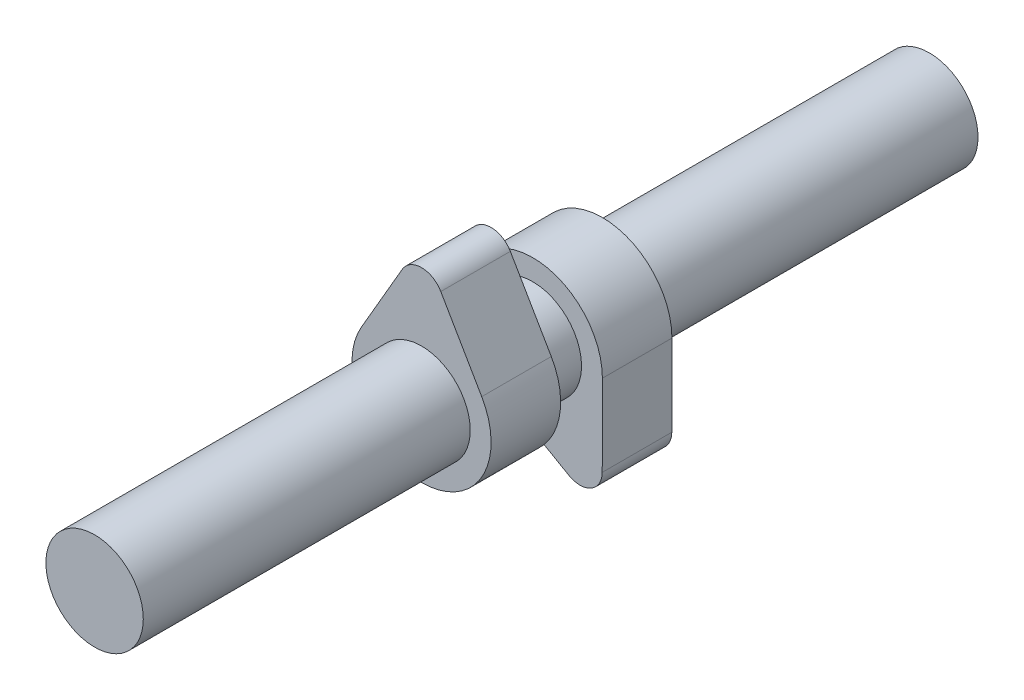
SolidWorks part; units mm, degrees
ref_plane "Front Plane" through (0, 0, 0) normal (0, 0, 1) x (1, 0, 0)
ref_plane "Top Plane" through (0, 0, 0) normal (0, 1, 0) x (1, 0, 0)
ref_plane "Right Plane" through (0, 0, 0) normal (1, 0, 0) x (0, 0, -1)
sketch "Sketch2" plane through (0, 0, 0) normal (0, 0, 1) x (1, 0, 0)
  circle A0 centre (0, 0) radius 17.5
  dimension "D1" = 35
extrude "Boss-Extrude1" add sketch "Sketch2" along normal mid plane 300 contours A0
sketch "Sketch3" plane through (0, 0, 150) normal (0, 0, 1) x (1, 0, 0)
  line L3 (-21.6293, 12.5369) -> (-6.9214, 37.9118)
  line L4 (6.9214, 37.9118) -> (21.6293, 12.5369)
  arc A1 (-6.9214, 37.9118) -> (6.9214, 37.9118) centre (0, 33.9) cw
  arc A3 (-21.6293, 12.5369) -> (21.6293, 12.5369) centre (0, 0) ccw
  circle A5 centre (0, 0) radius 25 construction
  point P2 (0, 41.9)
  circle M6 centre (0, 0) radius 17.5
  dimension "D1" = 8
  dimension "D2" = 25
  dimension "D3" = 16.9
extrude "Boss-Extrude2" add sketch "Sketch3" against normal mid plane 25 from offset 130 contours A1 M6 region at (-13.5527, 24.8055, 150) offset against normal yes
sketch "Sketch4" plane through (0, 0, 150) normal (0, 0, 1) x (1, 0, 0)
  line L0 (25, -0.0426) -> (24.95, -29.3719)
  line L1 (12.9618, -36.2933) -> (-12.4631, -21.6719)
  line L2 (-21.6293, 12.5369) -> (-6.9214, 37.9118) construction
  line L3 (6.9214, 37.9118) -> (21.6293, 12.5369) construction
  line L4 (0, 0) -> (0, -25) construction
  line L5 (16.95, -29.3583) -> (20.95, -36.2865) construction
  arc A0 (24.95, -29.3719) -> (12.9618, -36.2933) centre (16.95, -29.3583) cw
  arc A1 (25, -0.0426) -> (-12.4631, -21.6719) centre (0, 0) ccw
  arc A3 (-21.6293, 12.5369) -> (21.6293, 12.5369) centre (0, 0) ccw construction
  arc A4 (6.9214, 37.9118) -> (-6.9214, 37.9118) centre (0, 33.9) ccw construction
  dimension "D1" = 150
extrude "Boss-Extrude3" add sketch "Sketch4" along normal mid plane 25 from offset 170 offset against normal yes
equation "\"Camshaft Radius\"= 35mm'CHANGE LATER"
equation "\"Base Radius\"= 25mm'CHANGLE LATER"
equation "\"D1@Sketch2\"=\"Camshaft Radius\""
equation "\"D2@Sketch3\"=\"Base Radius\""
equation "\"Max Lift\"= 16.9mm"
equation "\"D3@Sketch3\"=\"Max Lift\""
equation "\"Lobe Offset Angle\"= 150deg"
equation "\"D1@Sketch4\"=\"Lobe Offset Angle\""
